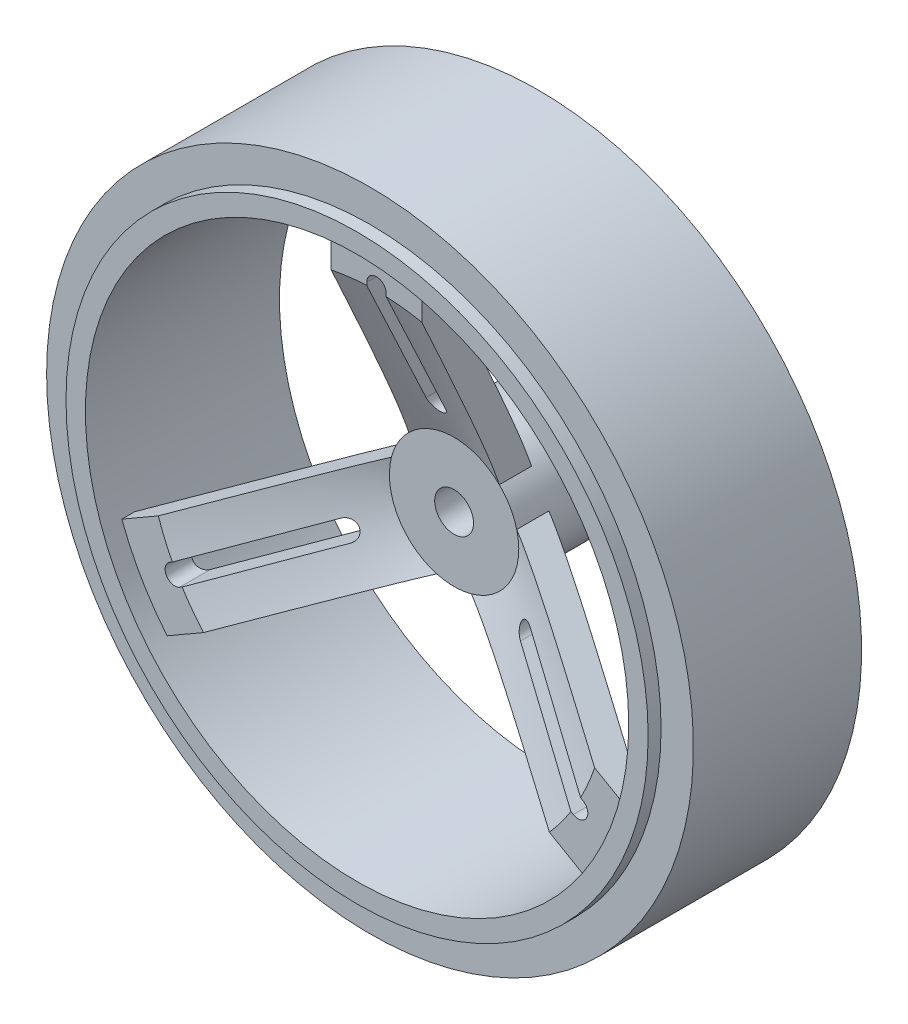
SolidWorks part; units mm, degrees
ref_plane "Front Plane" through (0, 0, 0) normal (0, 0, 1) x (1, 0, 0)
ref_plane "Top Plane" through (0, 0, 0) normal (0, 1, 0) x (1, 0, 0)
ref_plane "Right Plane" through (0, 0, 0) normal (1, 0, 0) x (0, 0, -1)
sketch "Sketch1" plane through (0, 0, 0) normal (0, 0, 1) x (1, 0, 0)
  circle A0 centre (0, 0) radius 50
  circle A1 centre (0, 0) radius 45
  circle A2 centre (0, 0) radius 42
  circle A3 centre (0, 0) radius 3
  circle A4 centre (0, 0) radius 10
  dimension "D1" = 100
  dimension "D4" = 6
  dimension "D5" = 20
  dimension "D2" = 5
  dimension "D3" = 3
extrude "Boss-Extrude1" add sketch "Sketch1" along normal mid plane 30 contours A1 A2 region at (-43.7272, 0, 0)
extrude "Boss-Extrude2" add sketch "Sketch1<3>" along normal blind 15 from surface separate body contours A4 A3 region at (-9.7172, 0, 0) starting at face at (42, 0, -15)
sketch "Sketch1<3>" plane through (0, 0, 0) normal (0, 0, 1) x (1, 0, 0) same geometry as "Sketch1"
sketch "Sketch2" plane through (0, 0, 0) normal (0, 0, 1) x (1, 0, 0)
  line L0 (0, 36) -> (0, 16) construction
  line L1 (-7, 44.4522) -> (7, 44.4522)
  line L2 (-7, 44.4522) -> (-7, 7.1414)
  line L3 (-7, 7.1414) -> (7, 7.1414)
  line L4 (7, 44.4522) -> (7, 7.1414)
  line L5 (1.5, 36) -> (1.5, 16)
  line L6 (-1.5, 36) -> (-1.5, 16)
  circle A1 centre (0, 0) radius 10 construction
  circle A2 centre (0, 0) radius 45 construction
  arc A3 (1.5, 36) -> (-1.5, 36) centre (0, 36) ccw
  arc A4 (-1.5, 16) -> (1.5, 16) centre (0, 16) ccw
  point P4 (0, 26)
  dimension "D1" = 3
  dimension "D2" = 20
  dimension "D3" = 16
  dimension "D4" = 14
extrude "Boss-Extrude3" add sketch "Sketch2" along normal blind 12 and the other way blind 5
pattern_circular "CirPattern1" count 3 over 360 about axis through (0, 0, 0) along (0, 0, -1) of "Boss-Extrude3" reverse direction yes
sketch "Sketch3" plane through (0, 0, 0) normal (1, 0, 0) x (0, 0, -1)
  line L0 (0, 0) -> (0, -10)
  line L1 (0, 0) -> (-15, 0)
  line L2 (-15, 0) -> (-15, -42)
  line L3 (0, -10) -> (-15, -42)
  line L4 (4.9699, -10) -> (15, -10)
  line L5 (15, -10) -> (15, -42)
  line L6 (15, -42) -> (-10.0301, -42)
  line L7 (-10.0301, -42) -> (4.9699, -10)
  dimension "D1" = 4.5
revolve "Cut-Revolve1" cut sketch "Sketch3" angle 360 about L1
extrude "Boss-Extrude4" add sketch "Sketch1<4>" along normal mid plane 26 contours A0 A1 region at (-48.5858, 0, 0)
sketch "Sketch1<4>" plane through (0, 0, 0) normal (0, 0, 1) x (1, 0, 0) same geometry as "Sketch1"
